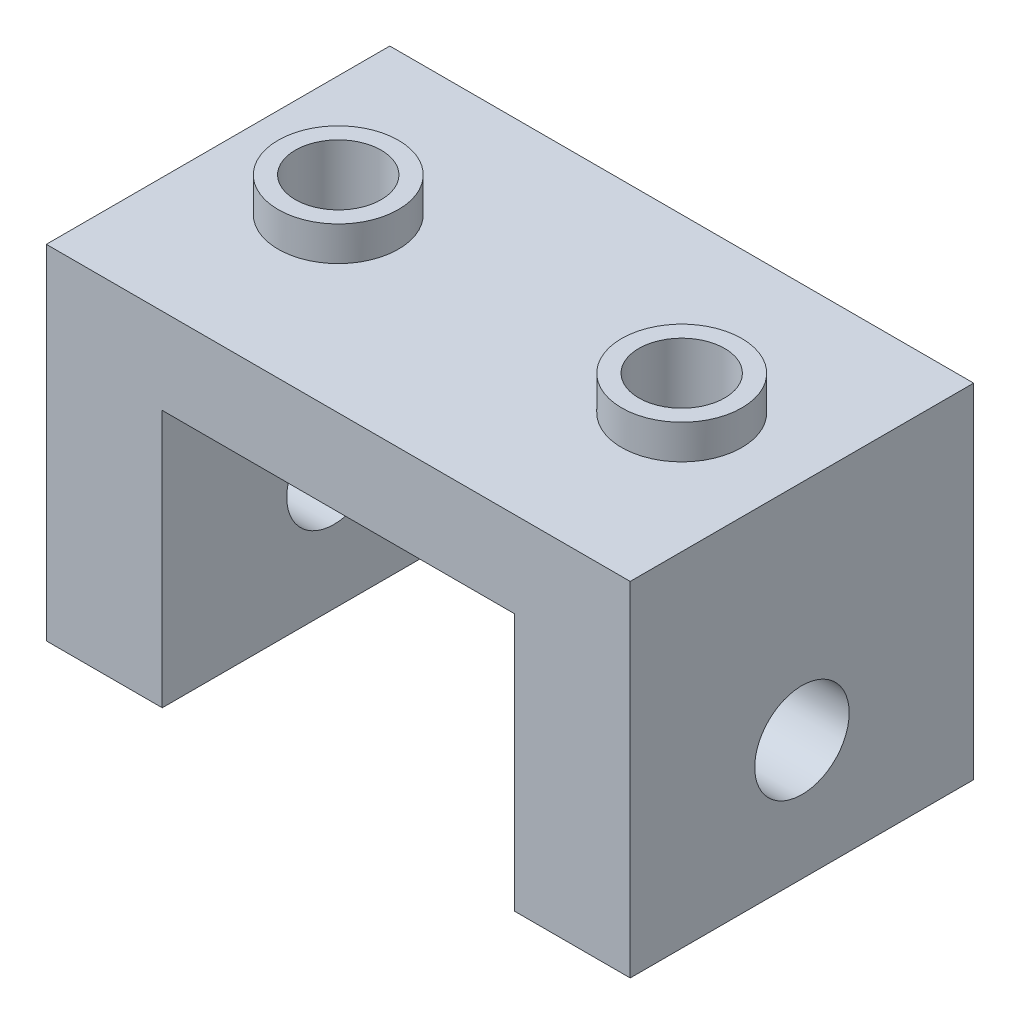
SolidWorks part; units mm, degrees
ref_plane "Front Plane" through (0, 0, 0) normal (0, 0, 1) x (1, 0, 0)
ref_plane "Top Plane" through (0, 0, 0) normal (0, 1, 0) x (1, 0, 0)
ref_plane "Right Plane" through (0, 0, 0) normal (1, 0, 0) x (0, 0, -1)
sketch "Sketch1" plane through (0, 0, 0) normal (0, 1, 0) x (1, 0, 0)
  line L1 (-17, 10) -> (17, 10)
  line L2 (-17, 10) -> (-17, -10)
  line L3 (-17, -10) -> (17, -10)
  line L4 (17, 10) -> (17, -10)
  line L5 (-17, 10) -> (17, -10) construction
  line L6 (-17, -10) -> (17, 10) construction
  point P0 (0, 0)
  dimension "D1" = 34
  dimension "D2" = 20
extrude "Boss-Extrude1" add sketch "Sketch1" along normal blind 5 contours L2 L3 L4 L1
sketch "Sketch2" plane through (0, 5, 0) normal (0, 1, 0) x (1, 0, 0)
  line L0 (-10, 0) -> (10, 0) construction
  circle A0 centre (-10, 0) radius 3.5
  circle A1 centre (10, 0) radius 3.5
  point P4 (0, 0)
  dimension "D2" = 7
  dimension "D1" = 20
extrude "Boss-Extrude2" add sketch "Sketch2" along normal blind 2
sketch "Sketch3" plane through (0, 7, 0) normal (0, 1, 0) x (1, 0, 0)
  circle A0 centre (-10, 0) radius 2.5
  circle A1 centre (10, 0) radius 2.5
  dimension "D1" = 5
extrude "Cut-Extrude1" cut sketch "Sketch3" against normal blind 4.5
sketch "Sketch4" plane through (0, 0, 0) normal (0, -1, 0) x (1, 0, 0)
  line L0 (-17, 10) -> (17, 10) construction
  line L1 (17, -10) -> (10.25, -10)
  line L2 (17, -10) -> (17, 10)
  line L3 (17, 10) -> (10.25, 10)
  line L4 (10.25, -10) -> (10.25, 10)
  line L6 (-17, -10) -> (-10.25, -10)
  line L7 (-17, -10) -> (-17, 10)
  line L8 (-17, 10) -> (-10.25, 10)
  line L9 (-10.25, -10) -> (-10.25, 10)
  dimension "D1" = 20.5
extrude "Boss-Extrude3" add sketch "Sketch4" along normal blind 15
sketch "Sketch5" plane through (17, 0, 0) normal (1, 0, 0) x (0, 0, -1)
  line L0 (0, -15) -> (0, -8) construction
  line L1 (10, -15) -> (-10, -15) construction
  dimension "D1" = 7
hole_wizard "M5 Clearance Hole1" positions "3DSketch1" profile "Sketch6" hole size "M5" standard "ANSI Metric" end condition through all
sketch3d "3DSketch1"
  point P0 (17, -8, 0)
sketch "Sketch6" plane through (17, -8, 0) normal (0, 1, 0) x (0, 0, -1)
  line L0 (0, 0) -> (0, 34)
  line L1 (0, 34) -> (2.75, 34)
  line L2 (2.75, 34) -> (2.75, 0)
  line L5 (2.75, 0) -> (0, 0)
  line L11 (0, -6.35) -> (0, 107.95) construction
  dimension "Thru Hole Dia." = 5.5
  dimension "Thru Hole Depth" = 34
